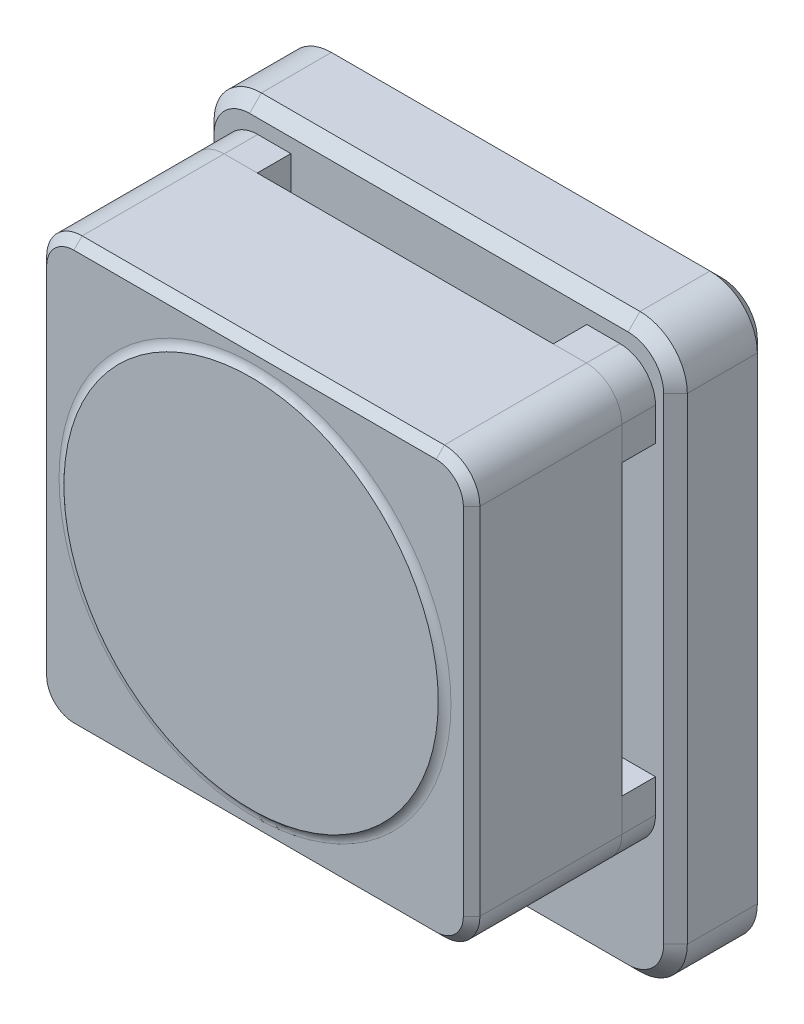
SolidWorks part; units mm, degrees
ref_plane "Front Plane" through (0, 0, 0) normal (0, 0, 1) x (1, 0, 0)
ref_plane "Top Plane" through (0, 0, 0) normal (0, 1, 0) x (1, 0, 0)
ref_plane "Right Plane" through (0, 0, 0) normal (1, 0, 0) x (0, 0, -1)
sketch "Sketch2" plane through (0, 0, 0) normal (0, 0, 1) x (1, 0, 0)
  line L1 (-15.31, -18) -> (15.31, -18)
  line L2 (-18.31, -15) -> (-18.31, 15)
  line L3 (-15.31, 18) -> (15.31, 18)
  line L4 (18.31, -15) -> (18.31, 15)
  line L5 (-18.31, -18) -> (18.31, 18) construction
  line L6 (-18.31, 18) -> (18.31, -18) construction
  arc A0 (-18.31, -15) -> (-15.31, -18) centre (-15.31, -15) ccw
  arc A1 (15.31, -18) -> (18.31, -15) centre (15.31, -15) ccw
  arc A2 (18.31, 15) -> (15.31, 18) centre (15.31, 15) ccw
  arc A3 (-15.31, 18) -> (-18.31, 15) centre (-15.31, 15) ccw
  point P0 (0, 0)
  dimension "D3" = 3
  dimension "D1" = 36.62
  dimension "D2" = 36
extrude "Boss-Extrude1" add sketch "Sketch2" along normal blind 12.7
sketch "Sketch7" plane through (0, 0, 12.7) normal (0, 0, 1) x (1, 0, 0)
  circle A0 centre (0, 0) radius 15.82
  dimension "D1" = 31.64
extrude "Boss-Extrude5" add sketch "Sketch7" along normal blind 0.33
fillet "Fillet1" radius 1 1 edges at (15.82, 0, 12.7)
chamfer "Chamfer1" distance 0.7 angle 45 8 edges at (-17.4313, 17.1213, 12.7) (0, 18, 12.7) (17.4313, 17.1213, 12.7) (18.31, 0, 12.7) (17.4313, -17.1213, 12.7) (0, -18, 12.7) (-17.4313, -17.1213, 12.7) (-18.31, 0, 12.7)
sketch "Sketch8" plane through (0, 0, 0) normal (0, 0, -1) x (-1, 0, 0)
  line L0 (-15.31, 18) -> (15.31, 18) construction
  line L1 (-12.51, 12.2) -> (-18.31, 12.2)
  line L2 (-12.51, 12.2) -> (-12.51, 18)
  line L3 (-12.51, 18) -> (-15.31, 18)
  line L4 (-18.31, 12.2) -> (-18.31, 15)
  line L5 (-18.31, -15) -> (-18.31, 15) construction
  line L6 (0, 18) -> (0, -18) construction
  line L7 (15.31, -18) -> (-15.31, -18) construction
  line L8 (-18.31, 0) -> (18.31, 0) construction
  line L9 (18.31, 15) -> (18.31, -15) construction
  line L10 (12.51, 18) -> (15.31, 18)
  line L11 (18.31, 12.2) -> (18.31, 15)
  line L12 (12.51, 12.2) -> (18.31, 12.2)
  line L13 (12.51, 12.2) -> (12.51, 18)
  line L14 (-12.51, -18) -> (-15.31, -18)
  line L15 (-18.31, -12.2) -> (-18.31, -15)
  line L16 (-12.51, -12.2) -> (-18.31, -12.2)
  line L17 (-12.51, -12.2) -> (-12.51, -18)
  line L18 (12.51, -12.2) -> (12.51, -18)
  line L19 (12.51, -12.2) -> (18.31, -12.2)
  line L20 (18.31, -12.2) -> (18.31, -15)
  line L21 (12.51, -18) -> (15.31, -18)
  arc A0 (-18.31, 15) -> (-15.31, 18) centre (-15.31, 15) cw
  arc A1 (18.31, 15) -> (15.31, 18) centre (15.31, 15) ccw
  arc A2 (-18.31, -15) -> (-15.31, -18) centre (-15.31, -15) ccw
  arc A3 (18.31, -15) -> (15.31, -18) centre (15.31, -15) cw
  dimension "D1" = 3
  dimension "D2" = 5.8
  dimension "D3" = 5.8
extrude "Boss-Extrude6" add sketch "Sketch8" along normal blind 2.84 separate body
sketch "Sketch9" plane through (0, 0, -2.84) normal (0, 0, -1) x (-1, 0, 0)
  line L0 (15.31, -18) -> (-15.31, -18) construction
  line L1 (-16, 20.2) -> (16, 20.2)
  line L2 (-20, 16.2) -> (-20, -24.12)
  line L3 (-16, -28.12) -> (16, -28.12)
  line L4 (20, 16.2) -> (20, -24.12)
  line L5 (18.31, 15) -> (18.31, -15) construction
  arc A0 (-20, -24.12) -> (-16, -28.12) centre (-16, -24.12) ccw
  arc A1 (20, -24.12) -> (16, -28.12) centre (16, -24.12) cw
  arc A2 (20, 16.2) -> (16, 20.2) centre (16, 16.2) ccw
  arc A3 (-20, 16.2) -> (-16, 20.2) centre (-16, 16.2) cw
  point P10 (-20, -28.12)
  point P15 (20, 20.2)
  point P18 (-20, 20.2)
  dimension "D5" = 4
  dimension "D1" = 40
  dimension "D2" = 48.32
  dimension "D3" = 10.12
  dimension "D4" = 1.69
extrude "Boss-Extrude7" add sketch "Sketch9" along normal blind 7.92
chamfer "Chamfer2" distance 1 angle 45 16 edges at (-20, -3.96, -10.76) (-18.8284, 19.0284, -10.76) (-18.8284, -26.9484, -10.76) (0, 20.2, -10.76) (0, -28.12, -10.76) (18.8284, 19.0284, -10.76) (18.8284, -26.9484, -10.76) (20, -3.96, -10.76) (-20, -3.96, -2.84) (-18.8284, 19.0284, -2.84) (-18.8284, -26.9484, -2.84) (0, 20.2, -2.84) (0, -28.12, -2.84) (18.8284, 19.0284, -2.84) (18.8284, -26.9484, -2.84) (20, -3.96, -2.84)
